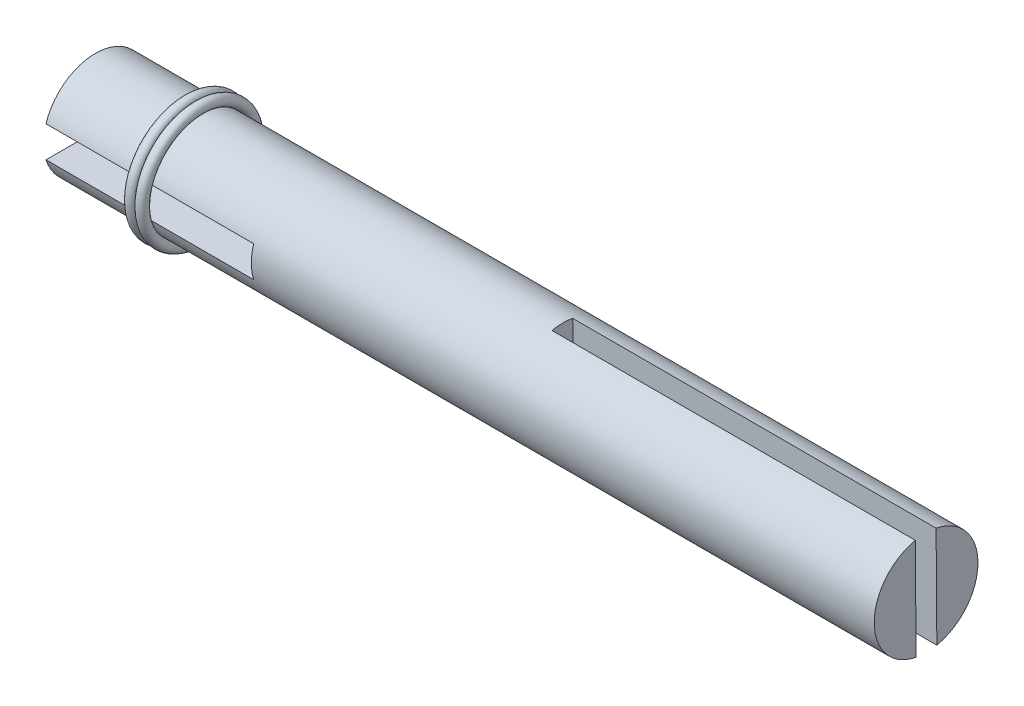
SolidWorks part; units mm, degrees
note: '?' marks a value the reader was unsure of.
ref_plane "前视基准面" through (0, 0, 0) normal (0, 0, 1) x (1, 0, 0)
ref_plane "上视基准面" through (0, 0, 0) normal (0, 1, 0) x (1, 0, 0)
ref_plane "右视基准面" through (0, 0, 0) normal (1, 0, 0) x (0, 0, -1)
sketch "草图1" plane through (0, 0, 0) normal (1, 0, 0) x (0, 0, -1)
  circle A0 centre (0, 0) radius 5
  dimension "D1" = 10
extrude "凸台-拉伸1" add sketch "草图1" along normal blind 80
sketch "草图2" plane through (0, 0, 0) normal (1, 0, 0) x (0, 0, -1)
  line L2 (-6.5805, 1.5) -> (-6.5805, -1.5)
  line L3 (-6.5805, -1.5) -> (7.0206, -1.5)
  line L4 (7.0206, -1.5) -> (7.0206, 1.5)
  line L5 (7.0206, 1.5) -> (-6.5805, 1.5)
extrude "切除-拉伸1" cut sketch "草图2" along normal blind 20
ref_plane "基准面1" through (80, 0, 0) normal (1, 0, 0) x (0, 0, -1)
sketch "草图3" plane through (80, 0, 0) normal (1, 0, 0) x (0, 0, -1)
  line L2 (-0.9999, -0.0091) -> (-0.9142, -12.0088)
  line L3 (-0.9142, -12.0088) -> (1.0858, -11.9945)
  line L4 (1.0858, -11.9945) -> (0.9143, 12.0049)
  line L5 (0.9143, 12.0049) -> (-1.0857, 11.9906)
  line L6 (-1.0857, 11.9906) -> (-0.9999, -0.0091)
  dimension "D5" = 2
  dimension "D6" = 2
extrude "切除-拉伸2" cut sketch "草图3" against normal blind 35
ref_plane "基准面2" through (10, 0, 0) normal (1, 0, 0) x (0, 0, -1)
sketch "草图4" plane through (10, 0, 0) normal (1, 0, 0) x (0, 0, -1)
  circle A0 centre (0, 0) radius 5.5
  dimension "D1" = 11
sketch "草图5" plane through (0, 0, 0) normal (0, 0, 1) x (1, 0, 0)
  line L0 (10, -5.5) -> (10, 5.5) construction
  circle A0 centre (10, 5.5) radius 0.5
  dimension "D1" = 1
surface "曲面-扫描1"
ref_plane "基准面4" through (9.5, 0, 0) normal (1, 0, 0) x (0, 0, -1)
mirror "镜向2" about plane through (9.5, 0, 0) normal (1, 0, 0) of bodies 109
ref_plane "基准面5" through (20, 0, 0) normal (-1, 0, 0) x (0, 0, 1)
ref_axis "基准轴1" through (-4, 0, 0) along (1, 0, 0)?
